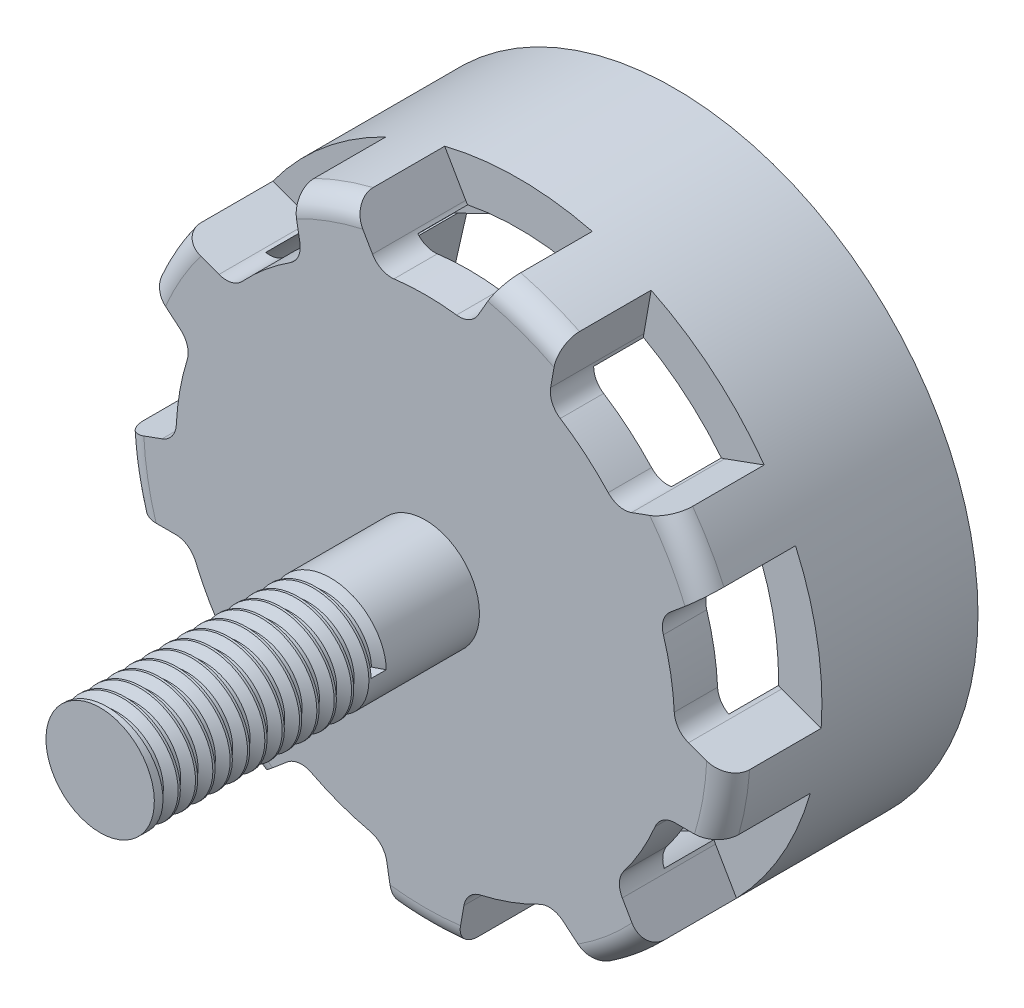
SolidWorks part; units mm, degrees
ref_plane "Спереди" through (0, 0, 0) normal (0, 0, 1) x (1, 0, 0)
ref_plane "Сверху" through (0, 0, 0) normal (0, 1, 0) x (1, 0, 0)
ref_plane "Справа" through (0, 0, 0) normal (1, 0, 0) x (0, 0, -1)
sketch "Эскиз1" plane through (0, 0, 0) normal (0, 0, 1) x (1, 0, 0)
  circle A0 centre (0, 0) radius 14
  circle A1 centre (0, 0) radius 12
  dimension "D1" = 28
  dimension "D2" = 2
extrude "Бобышка-Вытянуть1" add sketch "Эскиз1" along normal blind 11.5
sketch "Эскиз2" plane through (0, 0, 11.5) normal (0, 0, 1) x (1, 0, 0)
  circle A0 centre (0, 0) radius 14
extrude "Бобышка-Вытянуть2" add sketch "Эскиз2" against normal blind 2
sketch "Эскиз3" plane through (0, 0, 11.5) normal (0, 0, 1) x (1, 0, 0)
  line L0 (-3.4043, 13.5798) -> (-2.4352, 11.9011)
  line L1 (2.4352, 11.9011) -> (3.4043, 13.5798)
  line L2 (0, -1000) -> (0, 49000) construction
  line L3 (6.121, 12.591) -> (5.7844, 10.6821)
  line L4 (9.5153, 7.5515) -> (11.3368, 8.2144)
  line L5 (12.7823, 5.7107) -> (11.2975, 4.4648)
  line L6 (12.1432, -0.3316) -> (13.9646, -0.9945)
  line L7 (13.4626, -3.8416) -> (11.5243, -3.8416)
  line L8 (9.0891, -8.0595) -> (10.0583, -9.7381)
  line L9 (7.8436, -11.5965) -> (6.3587, -10.3505)
  line L10 (1.7821, -12.0163) -> (1.4455, -13.9252)
  line L11 (-1.4455, -13.9252) -> (-1.7821, -12.0163)
  line L12 (-6.3587, -10.3505) -> (-7.8436, -11.5965)
  line L13 (-10.0583, -9.7381) -> (-9.0891, -8.0595)
  line L14 (-11.5243, -3.8416) -> (-13.4626, -3.8416)
  line L15 (-13.9646, -0.9945) -> (-12.1432, -0.3316)
  line L16 (-11.2975, 4.4648) -> (-12.7823, 5.7107)
  line L17 (-11.3368, 8.2144) -> (-9.5153, 7.5515)
  line L18 (-5.7844, 10.6821) -> (-6.121, 12.591)
  arc A0 (3.4043, 13.5798) -> (-3.4043, 13.5798) centre (0, 0) ccw
  circle A1 centre (0, 0) radius 14 construction
  arc A2 (1.4436, 11.409) -> (-1.4436, 11.409) centre (0, 0) ccw
  arc A3 (1.4436, 11.409) -> (2.4352, 11.9011) centre (1.5691, 12.4011) ccw
  arc A4 (-1.4436, 11.409) -> (-2.4352, 11.9011) centre (-1.5691, 12.4011) cw
  arc A5 (11.3368, 8.2144) -> (6.121, 12.591) centre (0, 0) ccw
  arc A6 (8.4395, 7.8119) -> (6.2277, 9.6678) centre (0, 0) ccw
  arc A7 (8.4395, 7.8119) -> (9.5153, 7.5515) centre (9.1733, 8.4912) ccw
  arc A8 (6.2277, 9.6678) -> (5.7844, 10.6821) centre (6.7693, 10.5084) cw
  arc A9 (13.9646, -0.9945) -> (12.7823, 5.7107) centre (0, 0) ccw
  arc A10 (11.4864, 0.5595) -> (10.985, 3.4028) centre (0, 0) ccw
  arc A11 (11.4864, 0.5595) -> (12.1432, -0.3316) centre (12.4852, 0.6081) ccw
  arc A12 (10.985, 3.4028) -> (11.2975, 4.4648) centre (11.9402, 3.6987) cw
  arc A13 (10.0583, -9.7381) -> (13.4626, -3.8416) centre (0, 0) ccw
  arc A14 (9.1587, -6.9547) -> (10.6023, -4.4543) centre (0, 0) ccw
  arc A15 (9.1587, -6.9547) -> (9.0891, -8.0595) centre (9.9551, -7.5595) ccw
  arc A16 (10.6023, -4.4543) -> (11.5243, -3.8416) centre (11.5243, -4.8416) cw
  arc A17 (1.4455, -13.9252) -> (7.8436, -11.5965) centre (0, 0) ccw
  arc A18 (2.5456, -11.2147) -> (5.2587, -10.2272) centre (0, 0) ccw
  arc A19 (2.5456, -11.2147) -> (1.7821, -12.0163) centre (2.7669, -12.1899) ccw
  arc A20 (5.2587, -10.2272) -> (6.3587, -10.3505) centre (5.7159, -11.1166) cw
  arc A21 (-7.8436, -11.5965) -> (-1.4455, -13.9252) centre (0, 0) ccw
  arc A22 (-5.2587, -10.2272) -> (-2.5456, -11.2147) centre (0, 0) ccw
  arc A23 (-5.2587, -10.2272) -> (-6.3587, -10.3505) centre (-5.7159, -11.1166) ccw
  arc A24 (-2.5456, -11.2147) -> (-1.7821, -12.0163) centre (-2.7669, -12.1899) cw
  arc A25 (-13.4626, -3.8416) -> (-10.0583, -9.7381) centre (0, 0) ccw
  arc A26 (-10.6023, -4.4543) -> (-9.1587, -6.9547) centre (0, 0) ccw
  arc A27 (-10.6023, -4.4543) -> (-11.5243, -3.8416) centre (-11.5243, -4.8416) ccw
  arc A28 (-9.1587, -6.9547) -> (-9.0891, -8.0595) centre (-9.9551, -7.5595) cw
  arc A29 (-12.7823, 5.7107) -> (-13.9646, -0.9945) centre (0, 0) ccw
  arc A30 (-10.985, 3.4028) -> (-11.4864, 0.5595) centre (0, 0) ccw
  arc A31 (-10.985, 3.4028) -> (-11.2975, 4.4648) centre (-11.9402, 3.6987) ccw
  arc A32 (-11.4864, 0.5595) -> (-12.1432, -0.3316) centre (-12.4852, 0.6081) cw
  arc A33 (-6.121, 12.591) -> (-11.3368, 8.2144) centre (0, 0) ccw
  arc A34 (-6.2277, 9.6678) -> (-8.4395, 7.8119) centre (0, 0) ccw
  arc A35 (-6.2277, 9.6678) -> (-5.7844, 10.6821) centre (-6.7693, 10.5084) ccw
  arc A36 (-8.4395, 7.8119) -> (-9.5153, 7.5515) centre (-9.1733, 8.4912) cw
  point P80 (0, 0)
  dimension "D1" = 2.5
  dimension "D2" = 1
  dimension "D3" = 30
  dimension "D4" = 9
extrude "Вырез-Вытянуть1" cut sketch "Эскиз3" against normal blind 4.3
fillet "Скругление1" radius 1 9 edges at (-8.999, -10.7246, 11.5) (0, -14, 11.5) (8.999, -10.7246, 11.5) (13.7873, -2.4311, 11.5) (12.1244, 7, 11.5) (4.7883, 13.1557, 11.5) (-4.7883, 13.1557, 11.5) (-12.1244, 7, 11.5) (-13.7873, -2.4311, 11.5)
sketch "Эскиз4" plane through (0, 0, 11.5) normal (0, 0, 1) x (1, 0, 0)
  circle A0 centre (0, 0) radius 2.5
  dimension "D1" = 5
extrude "Бобышка-Вытянуть3" add sketch "Эскиз4" along normal blind 15
thread "Резьба1" pitch 0.8 method cut profile "Профиль резьбы1" start angle 2, offset 0, length 10, pitch 0.8, diameter 5
ref_plane "Плоскость4" through (-2.4985, 0.0872, 26.5) normal (-0.0349, -0.9994, 0) x (-0.9994, 0.0349, 0)
sketch "Профиль резьбы1" plane through (-2.4985, 0.0872, 26.5) normal (-0.0349, -0.9994, 0) x (-0.9994, 0.0349, 0)
  line L0 (0, 0) -> (0, 0.8) construction
  line L11 (0, 0) -> (0, 0.7)
  line L12 (0, 0.7) -> (-0.433, 0.45)
  line L13 (-0.433, 0.45) -> (-0.433, 0.25)
  line L15 (-0.433, 0.25) -> (0, 0)
  line L17 (-0.433, 0.35) -> (0, 0.35) construction
  point P2 (0, 0)
  dimension "Pitch" = 0.8
  dimension "Profile_Angle" = 60
  dimension "Profile_Land" = 0.2
  dimension "Profile_Height" = 0.433
sketch "Эскиз16" plane through (0, 0, 0) normal (0, 0, -1) x (-1, 0, 0)
  line L0 (0, -1000) -> (0, 49000) construction
  line L1 (-999.306, 12) -> (49000.694, 12) construction
  line L2 (3.0871, 11.5961) -> (7.1414, 9.6436)
  line L3 (-2.25, 11.7872) -> (2.25, 11.7872)
  line L4 (-2.25, 11.7872) -> (-2.25, 10.2872)
  line L5 (-2.25, 10.2872) -> (2.25, 10.2872)
  line L6 (2.25, 11.7872) -> (2.25, 10.2872)
  line L7 (-2.25, 11.7872) -> (2.25, 10.2872) construction
  line L8 (-2.25, 10.2872) -> (2.25, 11.7872) construction
  line L9 (3.0871, 11.5961) -> (2.4363, 10.2447)
  line L10 (2.4363, 10.2447) -> (6.4906, 8.2922)
  line L11 (7.1414, 9.6436) -> (6.4906, 8.2922)
  line L12 (3.0871, 11.5961) -> (6.4906, 8.2922) construction
  line L13 (2.4363, 10.2447) -> (7.1414, 9.6436) construction
  line L14 (7.8127, 9.1083) -> (10.6184, 5.5901)
  line L15 (7.8127, 9.1083) -> (6.64, 8.1731)
  line L16 (6.64, 8.1731) -> (9.4457, 4.6548)
  line L17 (10.6184, 5.5901) -> (9.4457, 4.6548)
  line L18 (7.8127, 9.1083) -> (9.4457, 4.6548) construction
  line L19 (6.64, 8.1731) -> (10.6184, 5.5901) construction
  line L20 (10.991, 4.8165) -> (11.9923, 0.4293)
  line L21 (10.991, 4.8165) -> (9.5286, 4.4827)
  line L22 (9.5286, 4.4827) -> (10.5299, 0.0955)
  line L23 (11.9923, 0.4293) -> (10.5299, 0.0955)
  line L24 (10.991, 4.8165) -> (10.5299, 0.0955) construction
  line L25 (9.5286, 4.4827) -> (11.9923, 0.4293) construction
  line L26 (11.9923, -0.4293) -> (10.991, -4.8165)
  line L27 (11.9923, -0.4293) -> (10.5299, -0.0955)
  line L28 (10.5299, -0.0955) -> (9.5286, -4.4827)
  line L29 (10.991, -4.8165) -> (9.5286, -4.4827)
  line L30 (11.9923, -0.4293) -> (9.5286, -4.4827) construction
  line L31 (10.5299, -0.0955) -> (10.991, -4.8165) construction
  line L32 (10.6184, -5.5901) -> (7.8127, -9.1083)
  line L33 (10.6184, -5.5901) -> (9.4457, -4.6548)
  line L34 (9.4457, -4.6548) -> (6.64, -8.1731)
  line L35 (7.8127, -9.1083) -> (6.64, -8.1731)
  line L36 (10.6184, -5.5901) -> (6.64, -8.1731) construction
  line L37 (9.4457, -4.6548) -> (7.8127, -9.1083) construction
  line L38 (7.1414, -9.6436) -> (3.0871, -11.5961)
  line L39 (7.1414, -9.6436) -> (6.4906, -8.2922)
  line L40 (6.4906, -8.2922) -> (2.4363, -10.2447)
  line L41 (3.0871, -11.5961) -> (2.4363, -10.2447)
  line L42 (7.1414, -9.6436) -> (2.4363, -10.2447) construction
  line L43 (6.4906, -8.2922) -> (3.0871, -11.5961) construction
  line L44 (2.25, -11.7872) -> (-2.25, -11.7872)
  line L45 (2.25, -11.7872) -> (2.25, -10.2872)
  line L46 (2.25, -10.2872) -> (-2.25, -10.2872)
  line L47 (-2.25, -11.7872) -> (-2.25, -10.2872)
  line L48 (2.25, -11.7872) -> (-2.25, -10.2872) construction
  line L49 (2.25, -10.2872) -> (-2.25, -11.7872) construction
  line L50 (-3.0871, -11.5961) -> (-7.1414, -9.6436)
  line L51 (-3.0871, -11.5961) -> (-2.4363, -10.2447)
  line L52 (-2.4363, -10.2447) -> (-6.4906, -8.2922)
  line L53 (-7.1414, -9.6436) -> (-6.4906, -8.2922)
  line L54 (-3.0871, -11.5961) -> (-6.4906, -8.2922) construction
  line L55 (-2.4363, -10.2447) -> (-7.1414, -9.6436) construction
  line L56 (-7.8127, -9.1083) -> (-10.6184, -5.5901)
  line L57 (-7.8127, -9.1083) -> (-6.64, -8.1731)
  line L58 (-6.64, -8.1731) -> (-9.4457, -4.6548)
  line L59 (-10.6184, -5.5901) -> (-9.4457, -4.6548)
  line L60 (-7.8127, -9.1083) -> (-9.4457, -4.6548) construction
  line L61 (-6.64, -8.1731) -> (-10.6184, -5.5901) construction
  line L62 (-10.991, -4.8165) -> (-11.9923, -0.4293)
  line L63 (-10.991, -4.8165) -> (-9.5286, -4.4827)
  line L64 (-9.5286, -4.4827) -> (-10.5299, -0.0955)
  line L65 (-11.9923, -0.4293) -> (-10.5299, -0.0955)
  line L66 (-10.991, -4.8165) -> (-10.5299, -0.0955) construction
  line L67 (-9.5286, -4.4827) -> (-11.9923, -0.4293) construction
  line L68 (-11.9923, 0.4293) -> (-10.991, 4.8165)
  line L69 (-11.9923, 0.4293) -> (-10.5299, 0.0955)
  line L70 (-10.5299, 0.0955) -> (-9.5286, 4.4827)
  line L71 (-10.991, 4.8165) -> (-9.5286, 4.4827)
  line L72 (-11.9923, 0.4293) -> (-9.5286, 4.4827) construction
  line L73 (-10.5299, 0.0955) -> (-10.991, 4.8165) construction
  line L74 (-10.6184, 5.5901) -> (-7.8127, 9.1083)
  line L75 (-10.6184, 5.5901) -> (-9.4457, 4.6548)
  line L76 (-9.4457, 4.6548) -> (-6.64, 8.1731)
  line L77 (-7.8127, 9.1083) -> (-6.64, 8.1731)
  line L78 (-10.6184, 5.5901) -> (-6.64, 8.1731) construction
  line L79 (-9.4457, 4.6548) -> (-7.8127, 9.1083) construction
  line L80 (-7.1414, 9.6436) -> (-3.0871, 11.5961)
  line L81 (-7.1414, 9.6436) -> (-6.4906, 8.2922)
  line L82 (-6.4906, 8.2922) -> (-2.4363, 10.2447)
  line L83 (-3.0871, 11.5961) -> (-2.4363, 10.2447)
  line L84 (-7.1414, 9.6436) -> (-2.4363, 10.2447) construction
  line L85 (-6.4906, 8.2922) -> (-3.0871, 11.5961) construction
  circle A0 centre (0, 0) radius 12 construction
  point P11 (0, 11.0372)
  point P18 (4.7889, 9.9442)
  point P23 (8.6292, 6.8816)
  point P28 (10.7605, 2.456)
  point P33 (10.7605, -2.456)
  point P38 (8.6292, -6.8816)
  point P43 (4.7889, -9.9442)
  point P48 (0, -11.0372)
  point P53 (-4.7889, -9.9442)
  point P58 (-8.6292, -6.8816)
  point P63 (-10.7605, -2.456)
  point P68 (-10.7605, 2.456)
  point P73 (-8.6292, 6.8816)
  point P78 (-4.7889, 9.9442)
  point P79 (0, 0)
  dimension "D1" = 4.5
  dimension "D2" = 1.5
  dimension "D3" = 14
extrude "Бобышка-Вытянуть4" add sketch "Эскиз16" against normal blind 5 separate body
